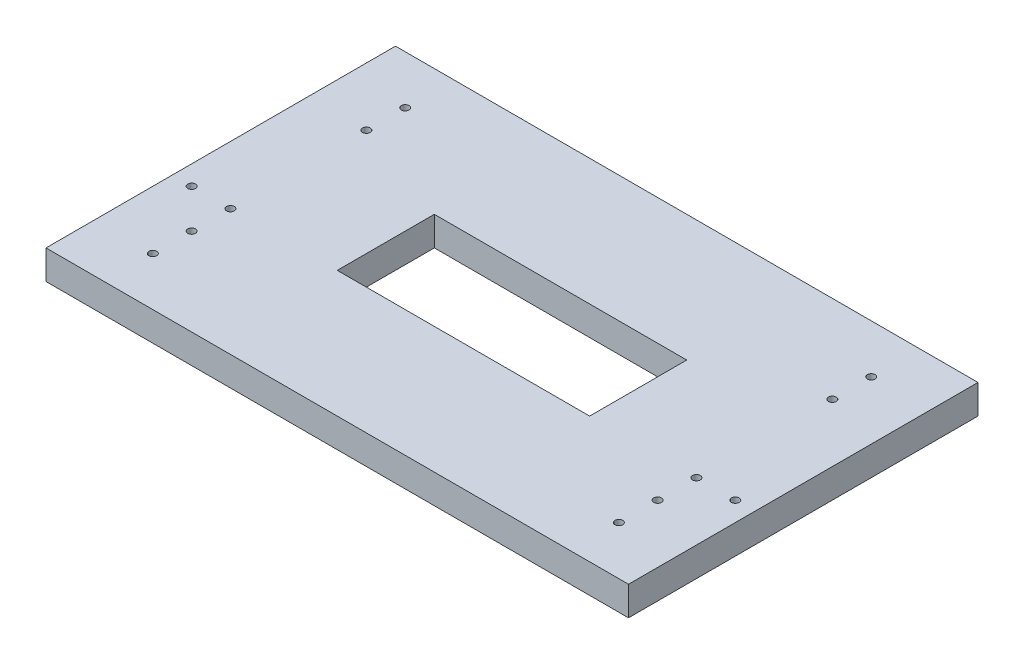
SolidWorks part; units mm, degrees
ref_plane "Alzado" through (0, 0, 0) normal (0, 0, 1) x (1, 0, 0)
ref_plane "Planta" through (0, 0, 0) normal (0, 1, 0) x (1, 0, 0)
ref_plane "Vista lateral" through (0, 0, 0) normal (1, 0, 0) x (0, 0, -1)
sketch "Croquis1" plane through (0, 0, 0) normal (0, 1, 0) x (1, 0, 0)
  line L1 (-150, -90) -> (150, -90)
  line L2 (-150, -90) -> (-150, 90)
  line L3 (-150, 90) -> (150, 90)
  line L4 (150, -90) -> (150, 90)
  line L5 (-150, -90) -> (150, 90) construction
  line L6 (-150, 90) -> (150, -90) construction
  point P0 (0, 0)
  dimension "D1" = 300
  dimension "D2" = 180
extrude "Saliente-Extruir1" add sketch "Croquis1" along normal blind 15
sketch "Croquis2" plane through (0, 15, 0) normal (0, 1, 0) x (1, 0, 0)
  line L0 (150, 90) -> (-150, 90) construction
  line L1 (-150, -90) -> (150, -90) construction
  line L2 (-150, 90) -> (-150, -90) construction
  line L3 (150, -90) -> (150, 90) construction
  circle A0 centre (-120, -45) radius 2
  circle A1 centre (-120, -65) radius 2
  circle A2 centre (120, -45) radius 2
  circle A3 centre (120, -65) radius 2
  circle A4 centre (-140, -25) radius 2
  circle A5 centre (-120, -25) radius 2
  circle A6 centre (120, -25) radius 2
  circle A7 centre (140, -25) radius 2
  circle A8 centre (-120, 65) radius 2
  circle A9 centre (-120, 45) radius 2
  circle A10 centre (120, 45) radius 2
  circle A11 centre (120, 65) radius 2
  dimension "D2" = 30
  dimension "D3" = 25
  dimension "D4" = 30
  dimension "D7" = 10
  dimension "D8" = 20
  dimension "D9" = 30
  dimension "D10" = 10
  dimension "D15" = 25
  dimension "D5" = 30
  dimension "D6" = 30
  dimension "D11" = 65
  dimension "D12" = 0
  dimension "D13" = 65
  dimension "D14" = 0
  dimension "D16" = 20
  dimension "D17" = 25
  dimension "D18" = 20
  dimension "D19" = 25
  dimension "D20" = 20
  dimension "D21" = 20
  dimension "D22" = 30
extrude "Cortar-Extruir1" cut sketch "Croquis2" against normal blind 10
sketch "Croquis3" plane through (0, 15, 0) normal (0, 1, 0) x (1, 0, 0)
  line L1 (-65, -25) -> (65, -25)
  line L2 (-65, -25) -> (-65, 25)
  line L3 (-65, 25) -> (65, 25)
  line L4 (65, -25) -> (65, 25)
  line L5 (-65, -25) -> (65, 25) construction
  line L6 (-65, 25) -> (65, -25) construction
  point P0 (0, 0)
extrude "Cortar-Extruir2" cut sketch "Croquis3" against normal up to surface (15 mm away) up to face at (0, 0, 0)
sketch "Croquis4" plane through (0, 0, 0) normal (0, -1, 0) x (1, 0, 0)
  line L2 (150, -90) -> (-150, -90) construction
  line L3 (150, 90) -> (150, -90) construction
  circle A0 centre (140, -65) radius 2
  dimension "D1" = 25
  dimension "D2" = 10
extrude "Cortar-Extruir3" cut sketch "Croquis4" against normal blind 10
